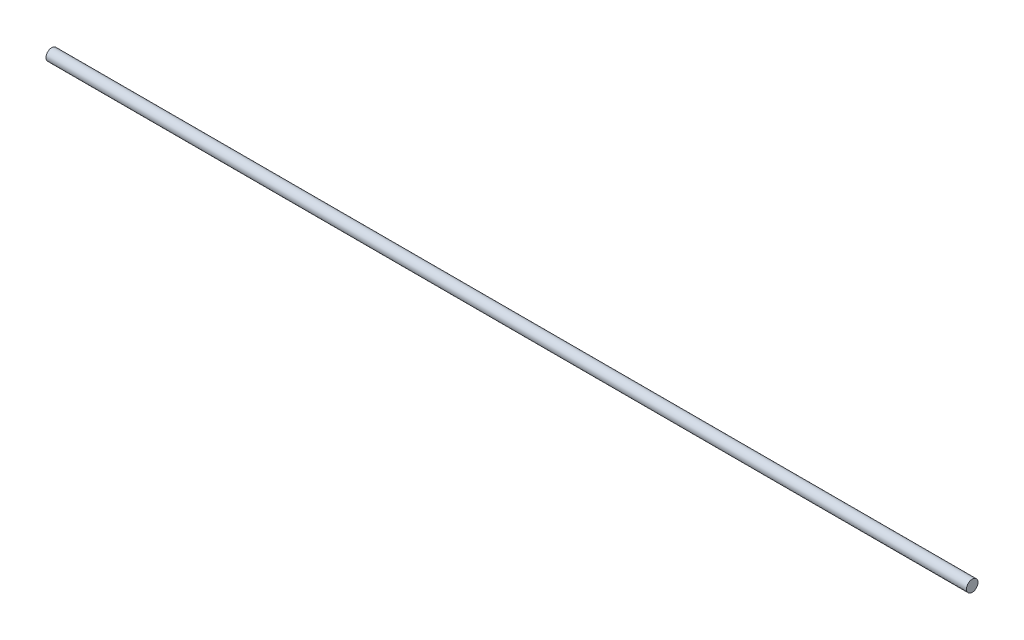
SolidWorks part; units mm, degrees
material "AISI Тип 316L нержавеющая сталь"
ref_plane "Спереди" through (0, 0, 0) normal (0, 0, 1) x (1, 0, 0)
ref_plane "Сверху" through (0, 0, 0) normal (0, 1, 0) x (1, 0, 0)
ref_plane "Справа" through (0, 0, 0) normal (1, 0, 0) x (0, 0, -1)
sketch "Эскиз1" plane through (0, 0, 0) normal (1, 0, 0) x (0, 0, -1)
  line L0 (0, 10) -> (0, -10) construction
  line L1 (0, 10) -> (8.0242, 10) construction
  line L2 (10, 0) -> (-10, 0) construction
  circle A0 centre (0, 0) radius 10
  dimension "D1" = 20
extrude "Бобышка-Вытянуть1" add sketch "Эскиз1" along normal mid plane 1600
sketch "Эскиз2" plane through (0, 0, 0) normal (0, 0, 1) x (1, 0, 0)
  line L0 (-800, 10) -> (800, 10) construction
  dimension "D1" = 1600
ref_plane "Плоскость1" through (0, 10, 0) normal (0, 1, 0) x (1, 0, 0)
